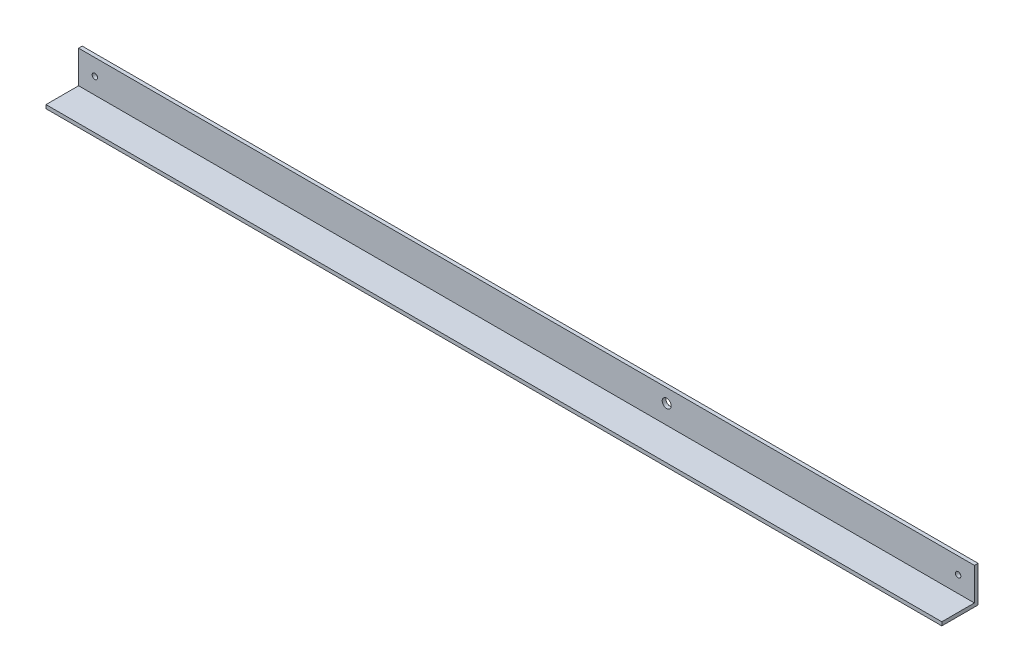
SolidWorks part; units mm, degrees
ref_plane "Front Plane" through (0, 0, 0) normal (0, 0, 1) x (1, 0, 0)
ref_plane "Top Plane" through (0, 0, 0) normal (0, 1, 0) x (1, 0, 0)
ref_plane "Right Plane" through (0, 0, 0) normal (1, 0, 0) x (0, 0, -1)
sketch "Sketch1" plane through (0, 0, 0) normal (1, 0, 0) x (0, 0, -1)
  line L0 (0, 20) -> (0, 0)
  line L1 (0, 0) -> (-20, 0)
  line L2 (-20, 0) -> (-20, 2)
  line L3 (-20, 2) -> (-2, 2)
  line L4 (-2, 2) -> (-2, 20)
  line L5 (-2, 20) -> (0, 20)
  dimension "D1" = 20
  dimension "D2" = 20
  dimension "D3" = 2
  dimension "D4" = 2
extrude "Boss-Extrude1" add sketch "Sketch1" along normal blind 170 and the other way blind 325
sketch "Sketch3" plane through (0, 0, 2) normal (0, 0, 1) x (1, 0, 0)
  line L0 (-325, 0) -> (170, 0) construction
  line L1 (-325, 20) -> (-325, 2) construction
  line L2 (-325, 20) -> (170, 20) construction
  line L3 (170, 20) -> (170, 2) construction
  circle A0 centre (0, 12.5) radius 2.5
  circle A1 centre (161, 11) radius 1.5
  circle A2 centre (-316, 11) radius 1.5
  dimension "D2" = 5
  dimension "D3" = 3
  dimension "D8" = 3
  dimension "D1" = 12.5
  dimension "D4" = 9
  dimension "D5" = 9
  dimension "D6" = 9
  dimension "D7" = 9
extrude "Cut-Extrude1" cut sketch "Sketch3" against normal blind 2
